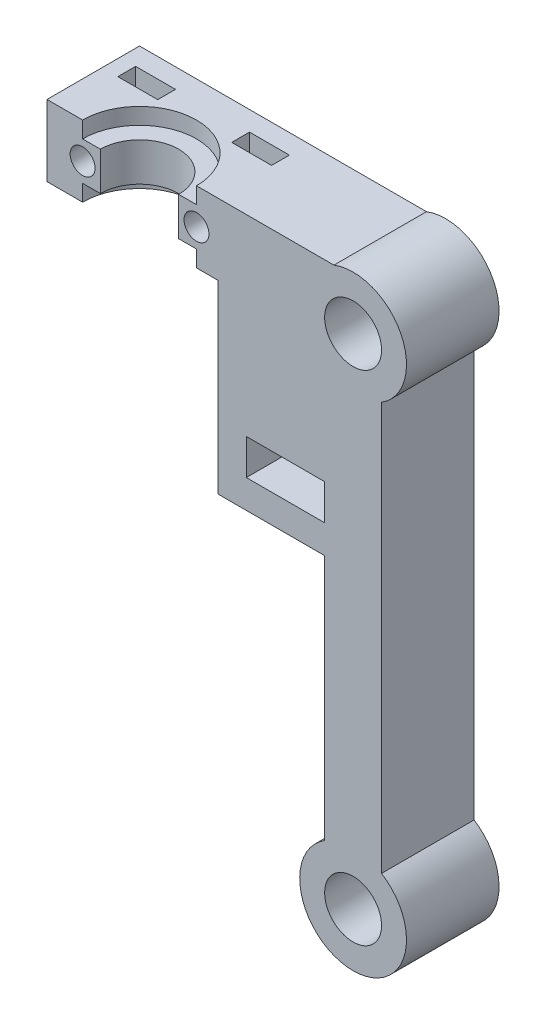
SolidWorks part; units mm, degrees
material "ABS"
ref_plane "Plano frontal" through (0, 0, 0) normal (0, 0, 1) x (1, 0, 0)
ref_plane "Plano superior" through (0, 0, 0) normal (0, 1, 0) x (1, 0, 0)
ref_plane "Plano direito" through (0, 0, 0) normal (1, 0, 0) x (0, 0, -1)
sketch "Esboço1" plane through (0, 0, 0) normal (0, 0, 1) x (1, 0, 0)
  line L0 (4, 63.6557) -> (4, 6.3443)
  line L1 (0, 70) -> (0, 0) construction
  line L2 (-2.6926, 77) -> (-19, 77)
  line L3 (-4, 41) -> (-19, 41)
  line L4 (-19, 41) -> (-19, 53)
  line L6 (-19, 77) -> (-19, 53)
  line L7 (-4, 41) -> (-4, 6.3443)
  line L8 (-15, 50) -> (-4, 50)
  line L9 (-15, 50) -> (-15, 45)
  line L10 (-15, 45) -> (-4, 45)
  line L11 (-4, 50) -> (-4, 45)
  line L12 (-15, 50) -> (-4, 45) construction
  line L13 (-15, 45) -> (-4, 50) construction
  circle A0 centre (0, 70) radius 4
  circle A1 centre (0, 0) radius 4
  arc A2 (4, 63.6557) -> (-2.6926, 77) centre (0, 70) ccw
  arc A3 (-4, 6.3443) -> (4, 6.3443) centre (0, 0) ccw
  point P4 (-9.5, 47.3933)
  point P6 (0, 0)
  point P12 (-11.5, 41)
  point P14 (-9.5, 47.5)
  dimension "D1" = 8
  dimension "D2" = 15
  dimension "D3" = 70
  dimension "D4" = 8
  dimension "D5" = 20
  dimension "D6" = 12
  dimension "D7" = 15
  dimension "D8" = 4
  dimension "D9" = 7
  dimension "D10" = 24
  dimension "D11" = 11
  dimension "D12" = 4
extrude "Ressalto-extrusão1" add sketch "Esboço1" along normal blind 13
sketch "Esboço5" plane through (0, 41, 0) normal (0, -1, 0) x (1, 0, 0)
  line L1 (-21, 13) -> (-19, 13)
  line L2 (-24.5, 13) -> (-21, 13)
  line L6 (-19, 13) -> (-19, 0)
  line L10 (-19, 0) -> (-43, 0)
  line L27 (-43, 0) -> (-43, 13)
  line L28 (-43, 13) -> (-35.5, 13)
  line L29 (-35.5, 13) -> (-24.5, 13) construction
  circle A0 centre (-30, 13) radius 9 construction
  arc A1 (-35.5, 13) -> (-24.5, 13) centre (-30, 13) ccw
  dimension "D11" = 5.5
  dimension "D2" = 18
  dimension "D3" = 7.5
  dimension "D4" = 24
extrude "Ressalto-extrusão3" add sketch "Esboço5" along normal blind 10 from offset 36 offset against normal yes
sketch "Esboço7" plane through (0, 77, 0) normal (0, 1, 0) x (1, 0, 0)
  circle A0 centre (-30, -13) radius 8
  dimension "D1" = 16
extrude "Corte-extrusão2" cut sketch "Esboço7" along normal blind 2.3 from offset 10 offset against normal yes
extrude "Corte-extrusão3" cut sketch "Esboço7<2>" against normal blind 2.3
sketch "Esboço7<2>" plane through (0, 77, 0) normal (0, 1, 0) x (1, 0, 0) same geometry as "Esboço7"
sketch "Esboço8" plane through (0, 77, 0) normal (0, 1, 0) x (1, 0, 0)
  line L0 (-38, -4) -> (-22, -4) construction
  line L1 (-40.8, -2.75) -> (-35.2, -2.75)
  line L2 (-40.8, -2.75) -> (-40.8, -5.25)
  line L3 (-40.8, -5.25) -> (-35.2, -5.25)
  line L4 (-35.2, -2.75) -> (-35.2, -5.25)
  line L5 (-40.8, -2.75) -> (-35.2, -5.25) construction
  line L6 (-40.8, -5.25) -> (-35.2, -2.75) construction
  line L7 (-24.8, -2.75) -> (-19.2, -2.75)
  line L8 (-24.8, -2.75) -> (-24.8, -5.25)
  line L9 (-24.8, -5.25) -> (-19.2, -5.25)
  line L10 (-19.2, -2.75) -> (-19.2, -5.25)
  line L11 (-24.8, -2.75) -> (-19.2, -5.25) construction
  line L12 (-24.8, -5.25) -> (-19.2, -2.75) construction
  line L13 (-36.5, -4) -> (-36.5, -14.5536) construction
  line L14 (-38, -13) -> (-43, -13) construction
  arc A0 (-22, -13) -> (-38, -13) centre (-30, -13) ccw construction
  point P0 (-38, -4)
  point P5 (-22, -4)
  point P12 (-30, -4)
  point P16 (-30, -5)
  dimension "D1" = 5.6
  dimension "D2" = 2.5
  dimension "D3" = 1.5
  dimension "D4" = 16
  dimension "D5" = 9
extrude "Corte-extrusão4" cut sketch "Esboço8" against normal blind 10
sketch "Esboço9" plane through (0, 0, 13) normal (0, 0, 1) x (1, 0, 0)
  line L0 (-22, 72) -> (-38, 72) construction
  line L1 (-22, 74.7) -> (-38, 74.7) construction
  line L2 (-35.5, 69.3) -> (-35.5, 74.7) construction
  circle A0 centre (-38, 72) radius 1.75
  circle A1 centre (-22, 72) radius 1.75
  point P4 (-30, 74.7)
  point P5 (-30, 72)
  point P10 (-35.5, 72)
  dimension "D1" = 3.5
  dimension "D2" = 16
extrude "Corte-extrusão5" cut sketch "Esboço9" against normal through all
